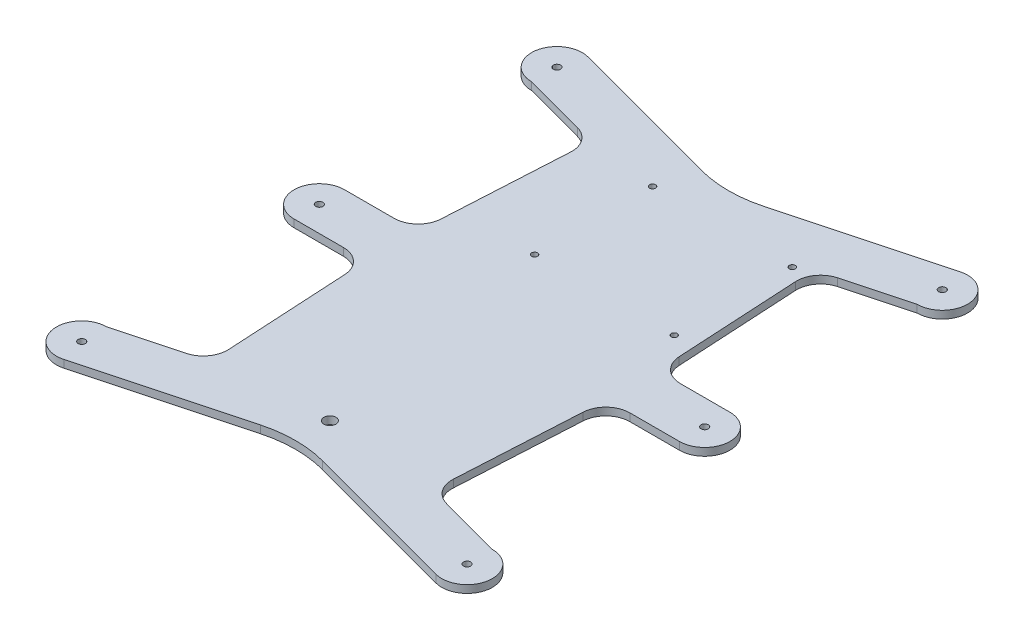
SolidWorks part; units mm, degrees
ref_plane "Front Plane" through (0, 0, 0) normal (0, 0, 1) x (1, 0, 0)
ref_plane "Top Plane" through (0, 0, 0) normal (0, 1, 0) x (1, 0, 0)
ref_plane "Right Plane" through (0, 0, 0) normal (1, 0, 0) x (0, 0, -1)
sketch "Sketch1" plane through (0, 0, 0) normal (0, 1, 0) x (1, 0, 0)
  line L0 (0, 32.1883) -> (0, -21.4181) construction
  line L1 (0, 0) -> (27.1703, 0) construction
  line L2 (-80, 10.5) -> (-50, 10.5)
  line L3 (-50, 10.5) -> (-46.1926, 79.0959)
  line L4 (-46.1926, 79.0959) -> (-80, 88.1546)
  line L5 (-77.2824, 108.7968) -> (0, 88.0891)
  line L6 (77.2824, 108.7968) -> (0, 88.0891)
  line L7 (46.1926, 79.0959) -> (80, 88.1546)
  line L8 (50, 10.5) -> (46.1926, 79.0959)
  line L9 (80, 10.5) -> (50, 10.5)
  line L10 (80, -10.5) -> (50, -10.5)
  line L11 (50, -10.5) -> (46.1926, -79.0959)
  line L12 (46.1926, -79.0959) -> (80, -88.1546)
  line L13 (77.2824, -108.7968) -> (0, -88.0891)
  line L14 (-77.2824, -108.7968) -> (0, -88.0891)
  line L15 (-46.1926, -79.0959) -> (-80, -88.1546)
  line L16 (-50, -10.5) -> (-46.1926, -79.0959)
  line L17 (-80, -10.5) -> (-50, -10.5)
  arc A0 (-80, 10.5) -> (-80, -10.5) centre (-80, 0) ccw
  arc A1 (-77.2824, 108.7968) -> (-80, 88.1546) centre (-80, 98.6546) ccw
  circle A2 centre (-80, 98.6546) radius 1.5
  circle A3 centre (-80, 0) radius 1.5
  circle A4 centre (80, 0) radius 1.5
  circle A5 centre (80, 98.6546) radius 1.5
  arc A6 (77.2824, 108.7968) -> (80, 88.1546) centre (80, 98.6546) cw
  arc A7 (80, 10.5) -> (80, -10.5) centre (80, 0) cw
  arc A8 (77.2824, -108.7968) -> (80, -88.1546) centre (80, -98.6546) ccw
  circle A9 centre (80, -98.6546) radius 1.5
  circle A10 centre (-80, -98.6546) radius 1.5
  arc A11 (-77.2824, -108.7968) -> (-80, -88.1546) centre (-80, -98.6546) cw
  dimension "D2" = 10.5
  dimension "D3" = 3
  dimension "D1" = 75
  dimension "D4" = 80
  dimension "D5" = 30
  dimension "D6" = 35
  dimension "D7" = 68.5959
extrude "Boss-Extrude1" add sketch "Sketch1" along normal blind 3.175
fillet "Fillet1" radius 50 2 edges at (0, 1.5875, -88.0891) (0, 1.5875, 88.0891)
fillet "Fillet2" radius 10 8 edges at (46.1926, 1.5875, 79.0959) (50, 1.5875, 10.5) (50, 1.5875, -10.5) (46.1926, 1.5875, -79.0959) (-46.1926, 1.5875, -79.0959) (-50, 1.5875, -10.5) (-50, 1.5875, 10.5) (-46.1926, 1.5875, 79.0959)
sketch "Sketch2" plane through (0, 3.175, 0) normal (0, 1, 0) x (1, 0, 0)
  line L0 (0, 89.8529) -> (0, -89.8529) construction
  line L2 (-17.25, 75.619) -> (40.75, 75.619) construction
  line L3 (-17.25, 75.619) -> (-17.25, 26.619) construction
  line L4 (-17.25, 26.619) -> (40.75, 26.619) construction
  line L5 (40.75, 75.619) -> (40.75, 26.619) construction
  line L6 (-17.25, 75.619) -> (-40.75, 75.619) construction
  line L7 (-17.25, 75.619) -> (-17.25, 26.619) construction
  line L8 (-17.25, 26.619) -> (-40.75, 26.619) construction
  line L9 (-40.75, 75.619) -> (-40.75, 26.619) construction
  arc A0 (-12.941, 91.5566) -> (12.941, 91.5566) centre (0, 139.8529) ccw construction
  arc A1 (12.941, -91.5566) -> (-12.941, -91.5566) centre (0, -139.8529) ccw construction
  circle A2 centre (-17.25, 75.619) radius 1.25
  circle A3 centre (40.75, 75.619) radius 1.25
  circle A4 centre (40.75, 26.619) radius 1.25
  circle A5 centre (-17.25, 26.619) radius 1.25
  circle A6 centre (0, -75.6029) radius 2.5
  dimension "D4" = 2.5
  dimension "D6" = 5
  dimension "D1" = 58
  dimension "D2" = 49
  dimension "D3" = 23.5
  dimension "D5" = 40.75
  dimension "D7" = 14.25
extrude "Cut-Extrude1" cut sketch "Sketch2" against normal through all both and the other way through all
